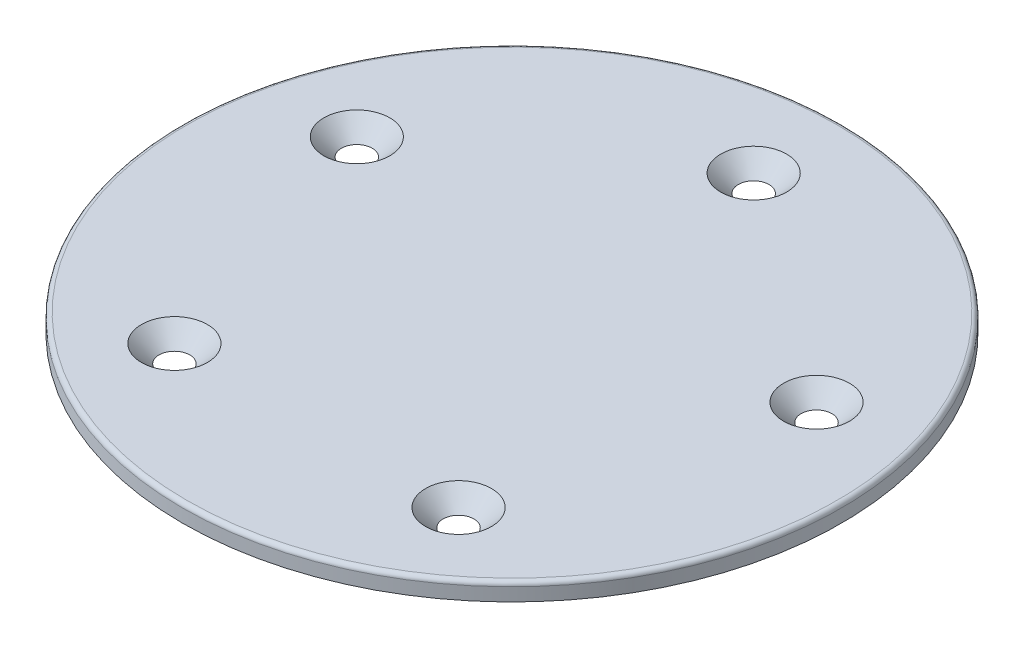
SolidWorks part; units mm, degrees
ref_plane "Front Plane" through (0, 0, 0) normal (0, 0, 1) x (1, 0, 0)
ref_plane "Top Plane" through (0, 0, 0) normal (0, 1, 0) x (1, 0, 0)
ref_plane "Right Plane" through (0, 0, 0) normal (1, 0, 0) x (0, 0, -1)
sketch "Sketch2" plane through (0, 0, 0) normal (0, 1, 0) x (1, 0, 0)
  circle A0 centre (0, 0) radius 37.5
  circle A1 centre (0, 0) radius 27.5
  circle A2 centre (0, 27.5) radius 1.75
  circle A3 centre (26.1541, 8.498) radius 1.75
  circle A4 centre (16.1641, -22.248) radius 1.75
  circle A5 centre (-16.1641, -22.248) radius 1.75
  circle A6 centre (-26.1541, 8.498) radius 1.75
  point P6 (0, 0)
  point P7 (0, 0)
  point P16 (0, 0)
  point P17 (0, 0)
  dimension "D1" = 75
  dimension "D2" = 55
  dimension "D4" = 3.5
  dimension "D3" = 5
extrude "Boss-Extrude1" add sketch "Sketch2" along normal blind 2 contours A0 A6 A1 A2 A3 A4 A5 | A6 A1 A5 A4 A3 A2 region at (-36.4393, 0, 0) region at (0, 0, 0)
chamfer "Chamfer1" distance 2 5 edges at (-16.1641, 2, 23.998) (16.1641, 2, 23.998) (26.1541, 2, -6.748) (0, 2, -25.75) (-26.1541, 2, -6.748)
fillet "Fillet1" radius 0.5 1 edges at (0, 2, 37.5)
